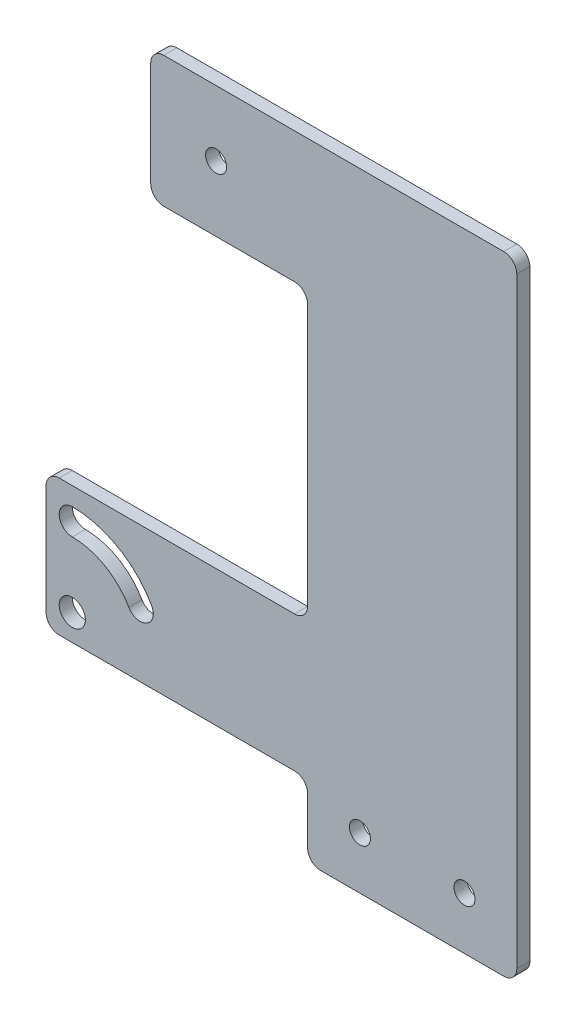
SolidWorks part; units mm, degrees
ref_plane "Front Plane" through (0, 0, 0) normal (0, 0, 1) x (1, 0, 0)
ref_plane "Top Plane" through (0, 0, 0) normal (0, 1, 0) x (1, 0, 0)
ref_plane "Right Plane" through (0, 0, 0) normal (1, 0, 0) x (0, 0, -1)
sketch "Sketch1" plane through (0, 0, 0) normal (0, 0, 1) x (1, 0, 0)
  line L0 (0, 50.8) -> (-63.5, 50.8)
  line L1 (0, 0) -> (50.8, 0)
  line L2 (0, 0) -> (0, 50.8)
  line L3 (0, 50.8) -> (50.8, 50.8)
  line L4 (50.8, 0) -> (50.8, 50.8)
  line L5 (-63.5, 50.8) -> (-63.5, 17.78)
  line L6 (-63.5, 17.78) -> (0, 17.78)
  line L7 (-57.15, 43.18) -> (-57.15, 24.13) construction
  line L8 (-57.15, 24.13) -> (-40.6522, 33.655) construction
  line L10 (0, 50.8) -> (50.8, 50.8)
  line L11 (0, 50.8) -> (0, 152.4)
  line L12 (0, 152.4) -> (50.8, 152.4)
  line L13 (50.8, 50.8) -> (50.8, 152.4)
  line L14 (0, 152.4) -> (-38.1, 152.4)
  line L15 (0, 152.4) -> (0, 120.65)
  line L16 (0, 120.65) -> (-38.1, 120.65)
  line L17 (-38.1, 152.4) -> (-38.1, 120.65)
  circle A0 centre (12.7, 12.7) radius 2.5527
  circle A1 centre (38.1, 12.7) radius 2.5527
  circle A2 centre (-57.15, 24.13) radius 3.175
  arc A4 (-57.15, 43.18) -> (-40.6522, 33.655) centre (-57.15, 24.13) cw construction
  arc A5 (-37.9026, 35.2425) -> (-57.15, 46.355) centre (-57.15, 24.13) ccw
  arc A6 (-43.4018, 32.0675) -> (-57.15, 40.005) centre (-57.15, 24.13) ccw
  arc A7 (-43.4018, 32.0675) -> (-37.9026, 35.2425) centre (-40.6522, 33.655) ccw
  arc A8 (-57.15, 46.355) -> (-57.15, 40.005) centre (-57.15, 43.18) ccw
  point P16 (-47.625, 40.6278)
  dimension "D3" = 5.1054
  dimension "D11" = 6.35
  dimension "D1" = 50.8
  dimension "D2" = 50.8
  dimension "D4" = 12.7
  dimension "D5" = 12.7
  dimension "D6" = 25.4
  dimension "D7" = 33.02
  dimension "D8" = 63.5
  dimension "D9" = 6.35
  dimension "D10" = 19.05
  dimension "D12" = 6.35
  dimension "D13" = 60
  dimension "D14" = 101.6
  dimension "D15" = 31.75
  dimension "D16" = 38.1
extrude "Boss-Extrude1" add sketch "Sketch1" along normal blind 3.175 contours L1 L4 L3 L2 A1 A0 | L5 L6 L2 L0 A8 A5 A7 A6 A2 region at (-29.9601, 34.0185, 0) region at (25.4, 25.6047, 0)
extrude "Boss-Extrude2" add sketch "Sketch1<4>" along normal blind 3.175 contours L3 L13 L12 L11 | L14 L17 L16 L11 region at (25.4, 101.6, 0) region at (-19.05, 136.525, 0)
sketch "Sketch1<4>" plane through (0, 0, 0) normal (0, 0, 1) x (1, 0, 0) same geometry as "Sketch1"
fillet "Fillet1" radius 3.175 10 edges at (50.8, 152.4, 1.5875) (50.8, 0, 1.5875) (0, 0, 1.5875) (0, 17.78, 1.5875) (-63.5, 17.78, 1.5875) (-63.5, 50.8, 1.5875) (0, 50.8, 1.5875) (0, 120.65, 1.5875) (-38.1, 120.65, 1.5875) (-38.1, 152.4, 1.5875)
sketch "Sketch2" plane through (0, 0, 3.175) normal (0, 0, 1) x (1, 0, 0)
  line L0 (-38.1, 149.225) -> (-38.1, 123.825) construction
  line L1 (-34.925, 152.4) -> (47.625, 152.4) construction
  circle A0 centre (-22.225, 136.525) radius 2.5527
  dimension "D1" = 5.1054
  dimension "D2" = 15.875
  dimension "D3" = 15.875
extrude "Cut-Extrude1" cut sketch "Sketch2" against normal blind 25.4
